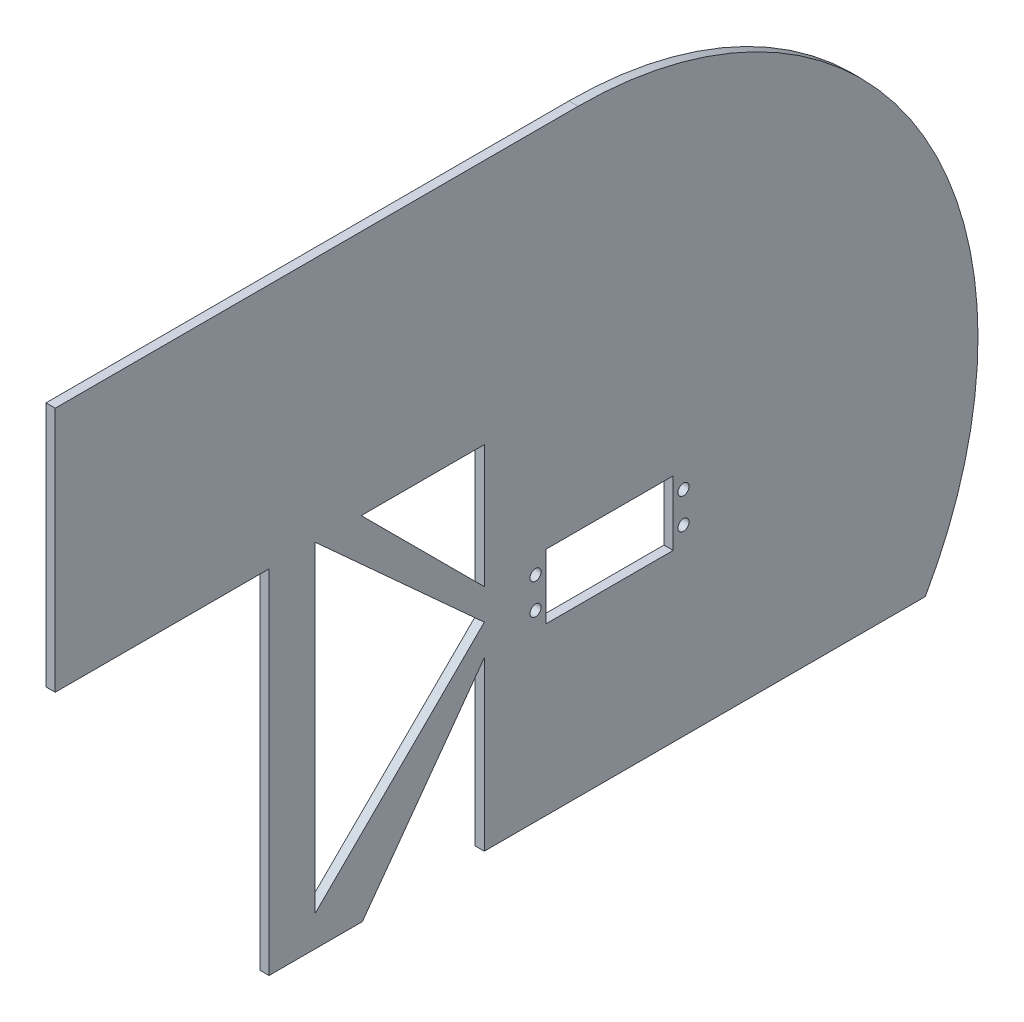
SolidWorks part; units mm, degrees
ref_plane "Front Plane" through (0, 0, 0) normal (0, 0, 1) x (1, 0, 0)
ref_plane "Top Plane" through (0, 0, 0) normal (0, 1, 0) x (1, 0, 0)
ref_plane "Right Plane" through (0, 0, 0) normal (1, 0, 0) x (0, 0, -1)
sketch "Sketch1" plane through (0, 0, 0) normal (1, 0, 0) x (0, 0, -1)
  line L0 (0, 130) -> (-170, 130)
  line L1 (-170, 130) -> (-170, 50)
  line L2 (-170, 50) -> (-120, 50)
  arc A0 (-120, 50) -> (0, 130) centre (0, 0) ccw
  circle A1 centre (0, 0) radius 5
  dimension "D1" = 260
  dimension "D2" = 10
  dimension "D3" = 80
  dimension "D4" = 170
extrude "Boss-Extrude1" add sketch "Sketch1" along normal blind 3
sketch "Sketch2" plane through (3, 0, 0) normal (1, 0, 0) x (0, 0, -1)
  line L0 (-10, 10) -> (-10, -10) construction
  line L1 (-10, -10) -> (30.4, -10) construction
  line L2 (30.4, -10) -> (30.4, 10) construction
  line L3 (30.4, 10) -> (-10, 10) construction
  line L4 (30.9, 10.5) -> (-10.5, 10.5)
  line L5 (-10.5, 10.5) -> (-10.5, -10.5)
  line L6 (-10.5, -10.5) -> (30.9, -10.5)
  line L7 (30.9, -10.5) -> (30.9, 10.5)
  circle A1 centre (0, 0) radius 5 construction
  circle A2 centre (-13.85, 5) radius 1.8
  circle A3 centre (-13.85, -5) radius 1.8
  circle A4 centre (34.25, 5) radius 1.8
  circle A5 centre (34.25, -5) radius 1.8
  point P11 (-10, 0)
  dimension "D1" = 10
  dimension "D2" = 10
  dimension "D4" = 3.6
  dimension "D7" = 3.85
  dimension "D8" = 5
  dimension "D10" = 5
  dimension "D12" = 3.85
  dimension "D13" = 10
  dimension "D3" = 40.4
  dimension "D5" = 20
  dimension "D9" = 10
  dimension "D11" = 3.85
  dimension "D6" = 0.5
extrude "ServoHole" cut sketch "Sketch2" against normal through all
sketch "Sketch3" plane through (3, 0, 0) normal (1, 0, 0) x (0, 0, -1)
  line L1 (123.9473, -130) -> (-198.7557, -130)
  line L2 (123.9473, -130) -> (123.9473, -64.5)
  line L3 (123.9473, -64.5) -> (-198.7557, -64.5)
  line L4 (-198.7557, -130) -> (-198.7557, -64.5)
  arc A0 (-120, 50) -> (0, 130) centre (0, 0) ccw construction
  dimension "D1" = 130
  dimension "D2" = 64.5
extrude "Cut-Extrude2" cut sketch "Sketch3" against normal through all
sketch "Sketch4" plane through (3, 0, 0) normal (1, 0, 0) x (0, 0, -1)
  line L1 (-170, 50) -> (-100.5, 50)
  line L2 (-170, 50) -> (-170, -65)
  line L3 (-170, -65) -> (-100.5, -65)
  line L4 (-30.5, 50) -> (-30.5, 10)
  line L5 (-10.5, 10.5) -> (-10.5, -10.5) construction
  line L6 (-70.5, 50) -> (-30.5, 10)
  line L7 (-85.5, 50) -> (-30.5, 0)
  line L8 (-30.5, 0) -> (-85.5, -54.5)
  line L9 (-30.5, -10) -> (-70.5, -65)
  line L10 (-70.5, 50) -> (-30.5, 50)
  line L11 (-30.5, -10) -> (-30.5, -65)
  line L12 (-70.5, -65) -> (-30.5, -65)
  line L13 (-85.5, 50) -> (-85.5, -54.5)
  line L14 (-100.5, 50) -> (-100.5, -65)
  line L15 (112.8705, -64.5) -> (-112.8705, -64.5) construction
  point P5 (-84.4519, -59.4914)
  point P18 (-271.4176, 17.0013)
  dimension "D1" = 20
  dimension "D2" = 40
  dimension "D3" = 45
  dimension "D4" = 10
  dimension "D5" = 10
  dimension "D6" = 15
  dimension "D7" = 15
  dimension "D8" = 40
  dimension "D9" = 15
  dimension "D10" = 10
  dimension "D11" = 115
extrude "Cut-Extrude5" cut sketch "Sketch4" against normal through all
